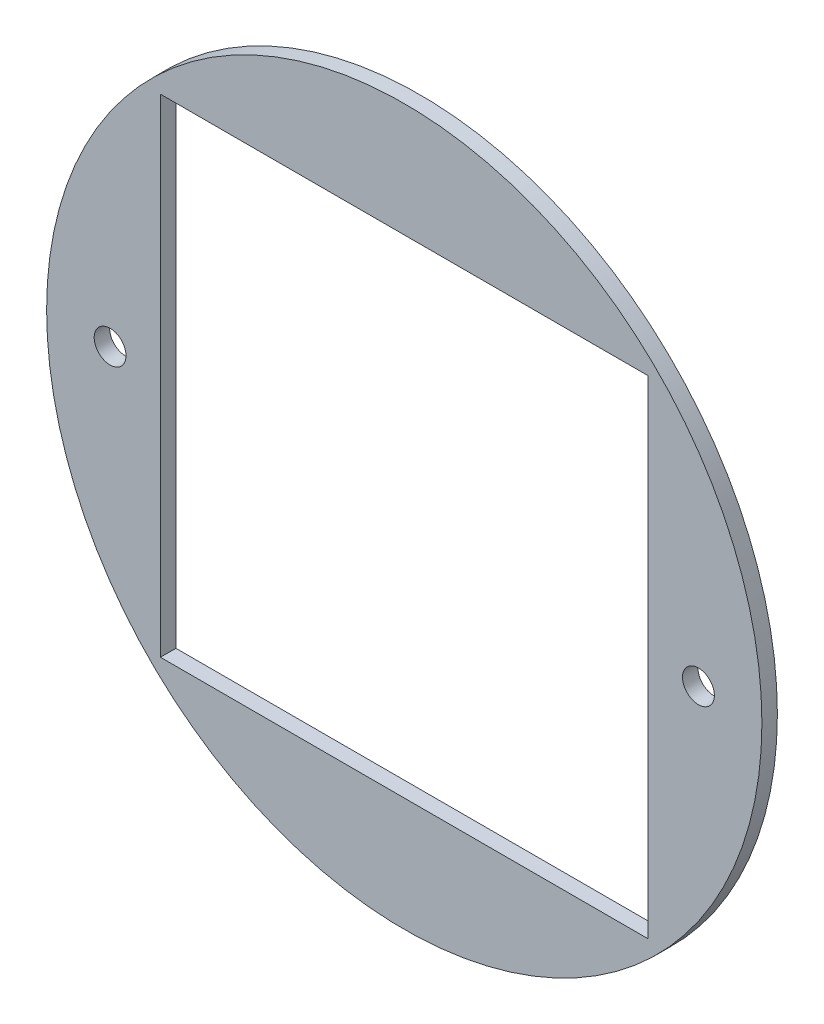
SolidWorks part; units mm, degrees
material "6061 Alloy"
ref_plane "Front Plane" through (0, 0, 0) normal (0, 0, 1) x (1, 0, 0)
ref_plane "Top Plane" through (0, 0, 0) normal (0, 1, 0) x (1, 0, 0)
ref_plane "Right Plane" through (0, 0, 0) normal (1, 0, 0) x (0, 0, -1)
sketch "Sketch1" plane through (0, 0, 0) normal (0, 0, 1) x (1, 0, 0)
  circle A0 centre (0, 0) radius 73.3425
  dimension "D1" = 146.685
extrude "Boss-Extrude1" add sketch "Sketch1" along normal blind 3.175
sketch "Sketch2" plane through (0, 0, 3.175) normal (0, 0, 1) x (1, 0, 0)
  point P0 (-60.325, 0)
  point P1 (60.325, 0)
  dimension "D1" = 60.325
  dimension "D2" = 60.325
hole_wizard "1/4 Clearance Hole1" positions "Sketch2" profile "Sketch3" hole size "1/4" standard "ANSI Inch" end condition through all
sketch "Sketch3" plane through (-60.325, 0, 3.175) normal (1, 0, 0) x (0, -1, 0)
  line L0 (0, 0) -> (0, 3.175)
  line L1 (0, 3.175) -> (3.2639, 3.175)
  line L2 (3.2639, 3.175) -> (3.2639, 0)
  line L5 (3.2639, 0) -> (0, 0)
  line L11 (0, -6.35) -> (0, 107.95) construction
  dimension "Thru Hole Dia." = 6.5278
  dimension "Thru Hole Depth" = 3.175
sketch "Sketch4" plane through (0, 0, 3.175) normal (0, 0, 1) x (1, 0, 0)
  line L1 (-50, -50) -> (50, -50)
  line L2 (-50, -50) -> (-50, 50)
  line L3 (-50, 50) -> (50, 50)
  line L4 (50, -50) -> (50, 50)
  line L5 (-50, -50) -> (50, 50) construction
  line L6 (-50, 50) -> (50, -50) construction
  point P0 (0, 0)
  dimension "D1" = 100
  dimension "D2" = 100
extrude "Cut-Extrude1" cut sketch "Sketch4" against normal through all both and the other way through all
equation "\"outerdiameter\"= 5.775"
equation "\"platethickness\"= 1 / 8"
equation "\"holespacing\"= 2.375"
equation "\"D1@Sketch1\"=\"outerdiameter\""
equation "\"D1@Boss-Extrude1\"=\"platethickness\""
equation "\"D1@Sketch2\"=\"holespacing\""
equation "\"D2@Sketch2\"=\"holespacing\""
equation "\"cutclearance\"= 100mm"
equation "\"D1@Sketch4\"=\"cutclearance\""
equation "\"D2@Sketch4\"=\"cutclearance\""
